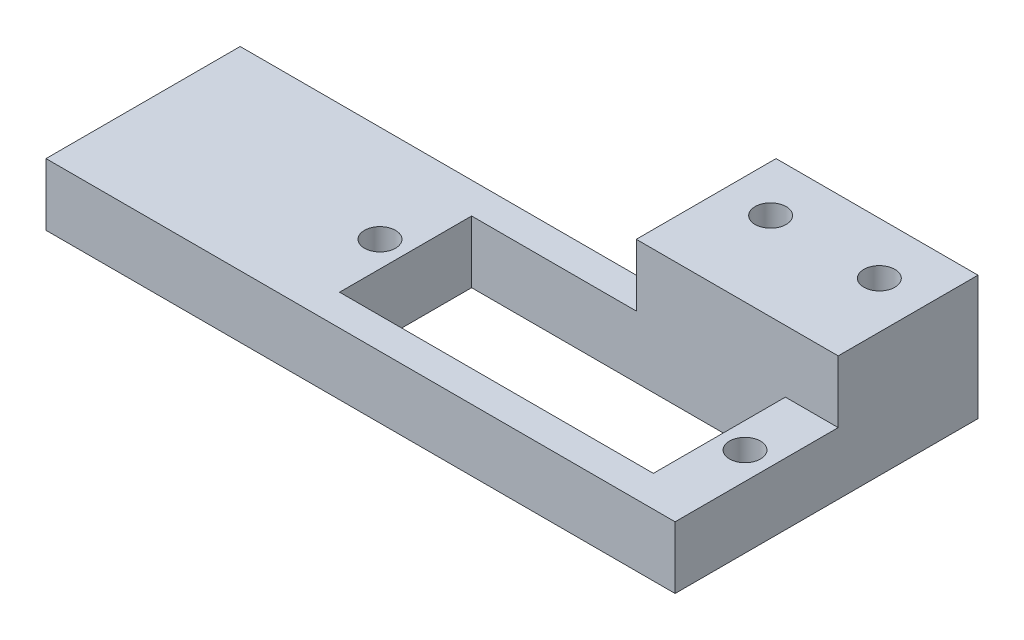
SolidWorks part; units mm, degrees
ref_plane "Płaszczyzna przednia" through (0, 0, 0) normal (0, 0, 1) x (1, 0, 0)
ref_plane "Płaszczyzna górna" through (0, 0, 0) normal (0, 1, 0) x (1, 0, 0)
ref_plane "Płaszczyzna prawa" through (0, 0, 0) normal (1, 0, 0) x (0, 0, -1)
sketch "Szkic1" plane through (0, 0, 0) normal (0, 1, 0) x (1, 0, 0)
  line L0 (-27, -0.5) -> (0.5, -0.5)
  line L1 (13.5, -13) -> (-27, -13)
  line L2 (13.5, -13) -> (13.5, 6.5)
  line L3 (13.5, 6.5) -> (0.5, 6.5)
  line L4 (-27, -13) -> (-27, -0.5)
  line L5 (13.5, -13) -> (0.5192, -0.5) construction
  line L6 (13.5, 6.5) -> (-27, -13) construction
  line L7 (10.1, -11) -> (-10.1, -11)
  line L8 (10.1, -11) -> (10.1, -2.5)
  line L9 (10.1, -2.5) -> (-10.1, -2.5)
  line L10 (-10.1, -11) -> (-10.1, -2.5)
  line L11 (10.1, -11) -> (-10.1, -2.5) construction
  line L12 (10.1, -2.5) -> (-10.1, -11) construction
  line L13 (0.5, -0.5) -> (0.5, 6.5)
  circle A0 centre (11.75, -6.75) radius 1
  circle A1 centre (-11.75, -6.75) radius 1
  circle A2 centre (3.5, 3.15) radius 1
  circle A3 centre (10.5, 3.15) radius 1
  point P0 (0, 0)
  point P1 (0, 0)
  point P6 (0, -6.75)
  dimension "D6" = 23.5
  dimension "D8" = 2
  dimension "D9" = 2
  dimension "D10" = 2
  dimension "D13" = 40.5
  dimension "D2" = 9
  dimension "D3" = 20.2
  dimension "D4" = 8.5
  dimension "D5" = 2
  dimension "D7" = 11.75
  dimension "D11" = 5.65
  dimension "D12" = 3
  dimension "D14" = 7
  dimension "D15" = 13
  dimension "D16" = 2
  dimension "D17" = 3.4
  dimension "D18" = 19.5
  dimension "D19" = 7
extrude "Dodanie-wyciągnięcie2" add sketch "Szkic1" along normal blind 4
sketch "Szkic3" plane through (0, 4, 0) normal (0, -1, 0) x (1, 0, 0)
  line L0 (10.1, 2.5) -> (-10.1, 2.5) construction
  line L1 (0.5, 2.5) -> (13.5, 2.5)
  line L2 (0.5, 2.5) -> (0.5, -6.5)
  line L3 (0.5, -6.5) -> (13.5, -6.5)
  line L4 (13.5, 2.5) -> (13.5, -6.5)
  line L5 (13.5, 13) -> (13.5, -6.5) construction
  dimension "D1" = 9
  dimension "D2" = 13
extrude "Dodanie-wyciągnięcie3" add sketch "Szkic3" against normal blind 4
extrude "Wytnij-wyciągnięcie2" cut sketch "Szkic1<3>" along normal through all contours A3 | A2 region at (10.5, 0, -3.15)
sketch "Szkic1<3>" plane through (0, 0, 0) normal (0, 1, 0) x (1, 0, 0) same geometry as "Szkic1"
sketch "Szkic4" plane through (-27, 0, 0) normal (-1, 0, 0) x (0, 0, 1)
  line L1 (0.5, 4) -> (13, 4) construction
  line L2 (0.5, 4) -> (0.5, 0) construction
  line L3 (13, 4) -> (13, 0) construction
  circle A0 centre (3.5, 2) radius 1
  circle A1 centre (10, 2) radius 1
  point P4 (0, 0)
  point P5 (0, 0)
  point P8 (0, 0)
  dimension "D1" = 2
  dimension "D2" = 2
  dimension "D3" = 2
  dimension "D4" = 2
  dimension "D5" = 3
  dimension "D6" = 3
extrude "Wytnij-wyciągnięcie3" cut sketch "Szkic4" against normal blind 10
